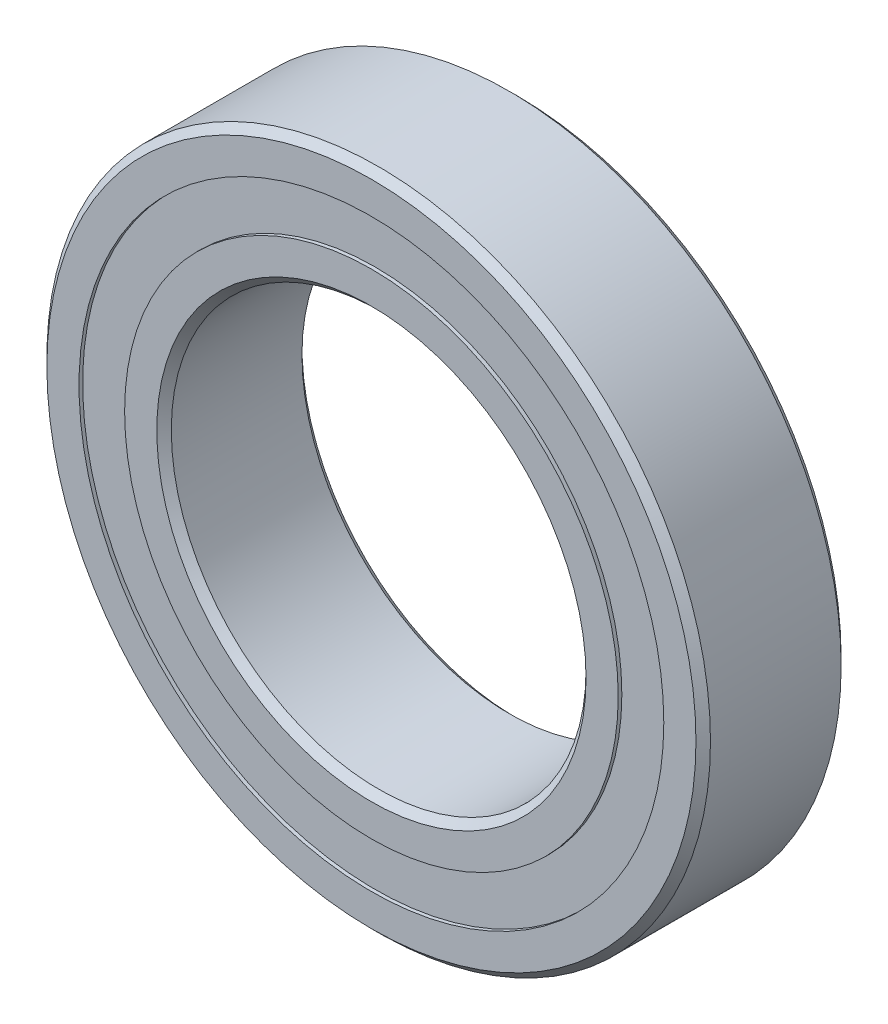
SolidWorks part; units mm, degrees
ref_plane "Front Plane" through (0, 0, 0) normal (0, 0, 1) x (1, 0, 0)
ref_plane "Top Plane" through (0, 0, 0) normal (0, 1, 0) x (1, 0, 0)
ref_plane "Right Plane" through (0, 0, 0) normal (1, 0, 0) x (0, 0, -1)
sketch "Sketch1" plane through (0, 0, 0) normal (1, 0, 0) x (0, 0, -1)
  line L0 (-3.5, 0) -> (3.5, 0) construction
  line L1 (0, 16) -> (0, -16) construction
  line L2 (3.15, 16) -> (-3.15, 16)
  line L3 (-3.15, 16) -> (-3.5, 15.65)
  line L4 (-3.5, 15.65) -> (-3.5, 14.0989)
  line L5 (-3.5, 14.0989) -> (-1.5556, 14.0989)
  line L6 (3.5, 14.0989) -> (1.5556, 14.0989)
  line L7 (3.5, 15.65) -> (3.5, 14.0989)
  line L8 (3.15, 16) -> (3.5, 15.65)
  line L9 (0, 16) -> (0, 13) construction
  line L10 (0, 13) -> (0, 10) construction
  arc A0 (-1.5556, 14.0989) -> (1.5556, 14.0989) centre (0, 13) cw
  point P14 (0, 10)
  dimension "D3" = 3.1111
  dimension "D1" = 45
  dimension "Width" = 7
  dimension "OD" = 32
  dimension "D2" = 0.35
  dimension "Shaft Dia" = 20
  dimension "D4" = 1.0989
revolve "Revolve1" add sketch "Sketch1" angle 360 about L0
sketch "Sketch3" plane through (0, 0, 0) normal (1, 0, 0) x (0, 0, -1)
  line L0 (-3.5, 11.9011) -> (-1.5556, 11.9011)
  line L1 (0, 16) -> (0, -16) construction
  line L2 (-3.5, 15.65) -> (-3.5, 14.0989) construction
  line L3 (-3.5, 11.9011) -> (-3.5, 10.35)
  line L4 (-3.15, 16) -> (-3.5, 15.65) construction
  line L5 (-3.5, 10.35) -> (-3.15, 10)
  line L6 (-3.15, 10) -> (3.15, 10)
  line L7 (3.15, 16) -> (3.15, -16) construction
  line L8 (3.15, 10) -> (3.5, 10.35)
  line L9 (3.5, -15.65) -> (3.5, 15.65) construction
  line L10 (3.5, 10.35) -> (3.5, 11.9011)
  line L11 (3.5, 11.9011) -> (1.5556, 11.9011)
  line L13 (3.15, 16) -> (3.5, 15.65) construction
  arc A0 (1.5556, 14.0989) -> (-1.5556, 14.0989) centre (0, 13) ccw construction
  arc A1 (1.5556, 11.9011) -> (-1.5556, 11.9011) centre (0, 13) cw
revolve "Revolve3" add sketch "Sketch3" angle 360 about L0
sketch "Sketch4" plane through (0, 0, 0) normal (1, 0, 0) x (0, 0, -1)
  line L0 (-1.9046, 13) -> (1.9046, 13)
  arc A2 (-1.9046, 13) -> (1.9046, 13) centre (0, 13) cw
  arc A3 (1.5556, 14.0989) -> (-1.5556, 14.0989) centre (0, 13) ccw construction
revolve "Revolve4" add sketch "Sketch4" angle 360 about L0
ref_axis "Axis1" through (0, 0, -3.5) along (0, 0, 1)
pattern_circular "CirPattern1" count 12 every 30 about axis through (0, 0, -3.5) along (0, 0, 1) of bodies 104
sketch "Sketch5" plane through (0, 0, 0) normal (1, 0, 0) x (0, 0, -1)
  line L0 (-3.5, 14.0989) -> (-1.5556, 14.0989) construction
  line L1 (-3.325, 14.0989) -> (-1.9046, 14.0989)
  line L2 (-3.325, 14.0989) -> (-3.325, 11.9011)
  line L3 (-3.325, 11.9011) -> (-1.9046, 11.9011)
  line L4 (-1.9046, 14.0989) -> (-1.9046, 11.9011)
  line L5 (-3.5, 11.9011) -> (-1.5556, 11.9011) construction
  line L6 (3.5, 14.0989) -> (1.5556, 14.0989) construction
  line L7 (3.325, 14.0989) -> (1.9046, 14.0989)
  line L8 (3.325, 14.0989) -> (3.325, 11.9011)
  line L9 (3.325, 11.9011) -> (1.9046, 11.9011)
  line L10 (1.9046, 14.0989) -> (1.9046, 11.9011)
  line L11 (3.5, 11.9011) -> (1.5556, 11.9011) construction
  line L12 (-3.15, 16) -> (-3.5, 15.65) construction
  point P18 (-3.325, 15.825)
revolve "Revolve5" add sketch "Sketch5" angle 360 about L0
equation "\"D2@Sketch1\" = \"Width@Sketch1\"*.05"
equation "\"D3@Sketch1\" = \"Width@Sketch1\"/2.25"
equation "\"D4@Sketch1\" = (((\"OD@Sketch1\"-\"Width@Sketch1\")/2)/3.25)/3.5"
equation "\"D2@CirPattern1\" = 360/\"Balls@CirPattern1\""
